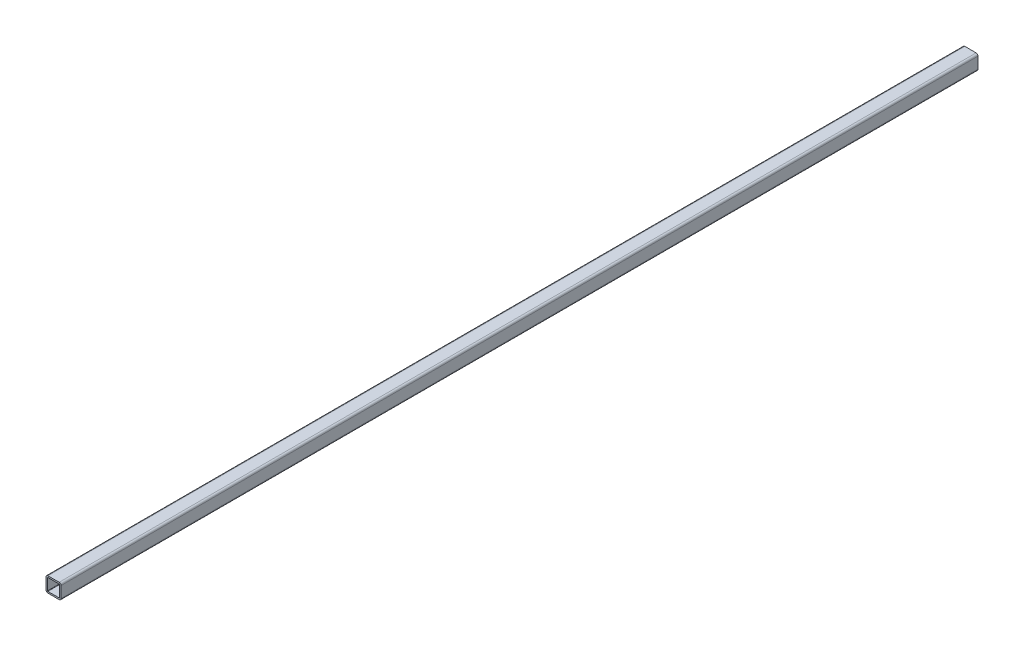
SolidWorks part; units mm, degrees
ref_plane "Front Plane" through (0, 0, 0) normal (0, 0, 1) x (1, 0, 0)
ref_plane "Top Plane" through (0, 0, 0) normal (0, 1, 0) x (1, 0, 0)
ref_plane "Right Plane" through (0, 0, 0) normal (1, 0, 0) x (0, 0, -1)
sketch "Sketch1" plane through (0, 0, 0) normal (0, 0, 1) x (1, 0, 0)
  line L1 (7.5, -10) -> (-7.5, -10)
  line L2 (10, -7.5) -> (10, 7.5)
  line L3 (7.5, 10) -> (-7.5, 10)
  line L4 (-10, -7.5) -> (-10, 7.5)
  line L5 (10, -10) -> (-10, 10) construction
  line L6 (10, 10) -> (-10, -10) construction
  arc A0 (-7.5, 10) -> (-10, 7.5) centre (-7.5, 7.5) ccw
  arc A1 (10, 7.5) -> (7.5, 10) centre (7.5, 7.5) ccw
  arc A2 (7.5, -10) -> (10, -7.5) centre (7.5, -7.5) ccw
  arc A3 (-7.5, -10) -> (-10, -7.5) centre (-7.5, -7.5) cw
  point P0 (0, 0)
  dimension "D2" = 2.5
  dimension "D1" = 20
extrude "Extrude-Thin1" add sketch "Sketch1" along normal mid plane 1219.2 thin thin type one direction reverse wall 2
equation "\"D2@Sketch1\" = \"D5@Extrude-Thin1\" * 1.25"
